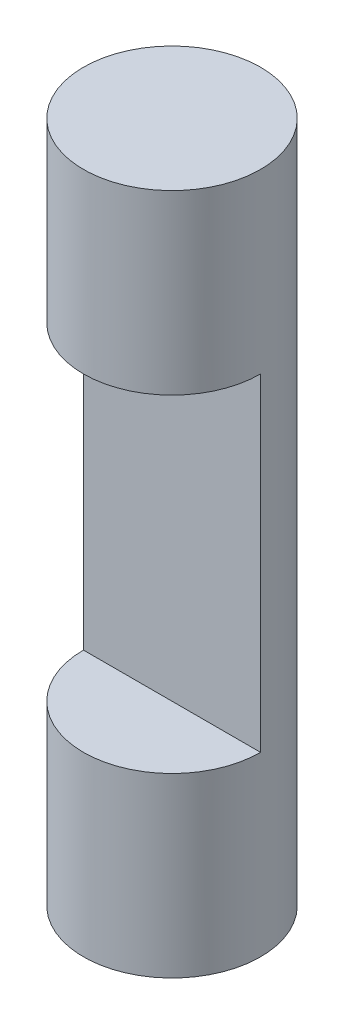
SolidWorks part; units mm, degrees
material "ABS"
ref_plane "Front Plane" through (0, 0, 0) normal (0, 0, 1) x (1, 0, 0)
ref_plane "Top Plane" through (0, 0, 0) normal (0, 1, 0) x (1, 0, 0)
ref_plane "Right Plane" through (0, 0, 0) normal (1, 0, 0) x (0, 0, -1)
sketch "Sketch1" plane through (0, 0, 0) normal (0, 1, 0) x (1, 0, 0)
  circle A0 centre (0, 0) radius 13
  dimension "D1" = 26
extrude "Boss-Extrude1" add sketch "Sketch1" along normal blind 1
ref_plane "Plane1" through (0, 1, 0) normal (0, 1, 0) x (1, 0, 0)
ref_plane "Plane2" through (0, 4.7, 0) normal (0, 1, 0) x (1, 0, 0)
ref_plane "Plane3" through (0, 9.7, 0) normal (0, 1, 0) x (1, 0, 0)
ref_plane "Plane4" through (0, 13.4, 0) normal (0, 1, 0) x (1, 0, 0)
ref_plane "Plane5" through (0, 18.4, 0) normal (0, 1, 0) x (1, 0, 0)
ref_plane "Plane6" through (0, 22.1, 0) normal (0, 1, 0) x (1, 0, 0)
ref_plane "Plane7" through (0, 27.1, 0) normal (0, 1, 0) x (1, 0, 0)
ref_plane "Plane8" through (0, 30.8, 0) normal (0, 1, 0) x (1, 0, 0)
sketch "Sketch16" plane through (0, 30.8, 0) normal (0, 1, 0) x (1, 0, 0)
  circle A0 centre (0, 0) radius 13
  circle A1 centre (0, 0) radius 13 construction
  dimension "D1" = 0
extrude "Boss-Extrude3" add sketch "Sketch16" along normal blind 1 separate body
sketch "Sketch18" plane through (0, 4.7, 0) normal (0, 1, 0) x (1, 0, 0)
  line L1 (-11, -11) -> (11, -11)
  line L2 (-11, -11) -> (-11, 11)
  line L3 (-11, 11) -> (11, 11)
  line L4 (11, -11) -> (11, 11)
  dimension "D1" = 22
  dimension "D2" = 22
  dimension "D3" = 11
  dimension "D4" = 11
sketch "Sketch19" plane through (0, 1, 0) normal (0, 1, 0) x (1, 0, 0)
  circle A0 centre (0, 11) radius 1
  point P13 (0, 0)
  dimension "D1" = 2
  dimension "D2" = 11
extrude "Boss-Extrude4" add sketch "Sketch19" along normal up to surface (29.8 mm away) up to face at (0, 30.8, 13)
extrude "Cut-Extrude6" cut sketch "Sketch18" against normal blind 3.7
sketch "Sketch21" plane through (0, 13.4, 0) normal (0, 1, 0) x (1, 0, 0)
  circle A0 centre (0, 0) radius 11
  dimension "D1" = 22
extrude "Cut-Extrude7" cut sketch "Sketch21" against normal blind 3.7
sketch "Sketch22" plane through (0, 22.1, 0) normal (0, 1, 0) x (1, 0, 0)
  circle A0 centre (0, 0) radius 11
  dimension "D1" = 22
extrude "Cut-Extrude8" cut sketch "Sketch22" against normal blind 3.7
sketch "Sketch23" plane through (0, 30.8, 0) normal (0, 1, 0) x (1, 0, 0)
  circle A0 centre (0, 0) radius 11
  dimension "D1" = 22
extrude "Cut-Extrude9" cut sketch "Sketch23" against normal blind 3.7
sketch "Sketch24" plane through (0, 31.8, 0) normal (0, 1, 0) x (1, 0, 0)
  circle A0 centre (0, 0) radius 19.9218
extrude "Cut-Extrude10" cut sketch "Sketch24" against normal blind 1
sketch "Sketch25" plane through (0, 1, 0) normal (0, 1, 0) x (1, 0, 0)
  circle A0 centre (0, 0) radius 36.1829
extrude "Cut-Extrude11" cut sketch "Sketch25" against normal blind 1
sketch "Sketch26" plane through (0, 30.8, 0) normal (0, 1, 0) x (1, 0, 0)
  circle A0 centre (0, 11) radius 1
  arc A1 (0.999, 10.9545) -> (-0.999, 10.9545) centre (0, 0) ccw construction
  arc A2 (0.999, 10.9545) -> (-0.999, 10.9545) centre (0, 11) ccw construction
  arc M1 (0.999, 10.9545) -> (-0.999, 10.9545) centre (0, 11) ccw
  arc M2 (-0.999, 10.9545) -> (0.999, 10.9545) centre (0, 0) cw
  dimension "D1" = 0
extrude "Boss-Extrude5" add sketch "Sketch26" along normal blind 2 contours M2 M1 | A0 M2 region at (0, 30.8, -11.4161) region at (0, 30.8, -10.5675)
sketch "Sketch27" plane through (0, 1, 0) normal (0, -1, 0) x (1, 0, 0)
  circle A0 centre (0, -11) radius 1
extrude "Boss-Extrude6" add sketch "Sketch27" along normal blind 2
sketch "Sketch28" plane through (0, 32.8, 0) normal (0, 1, 0) x (1, 0, 0)
  circle A0 centre (-0.3752, 0) radius 15.8574
extrude "Cut-Extrude12" cut sketch "Sketch28" against normal offset from surface (26.1 mm away) 2 up to face at (0, 4.7, -10.5)
